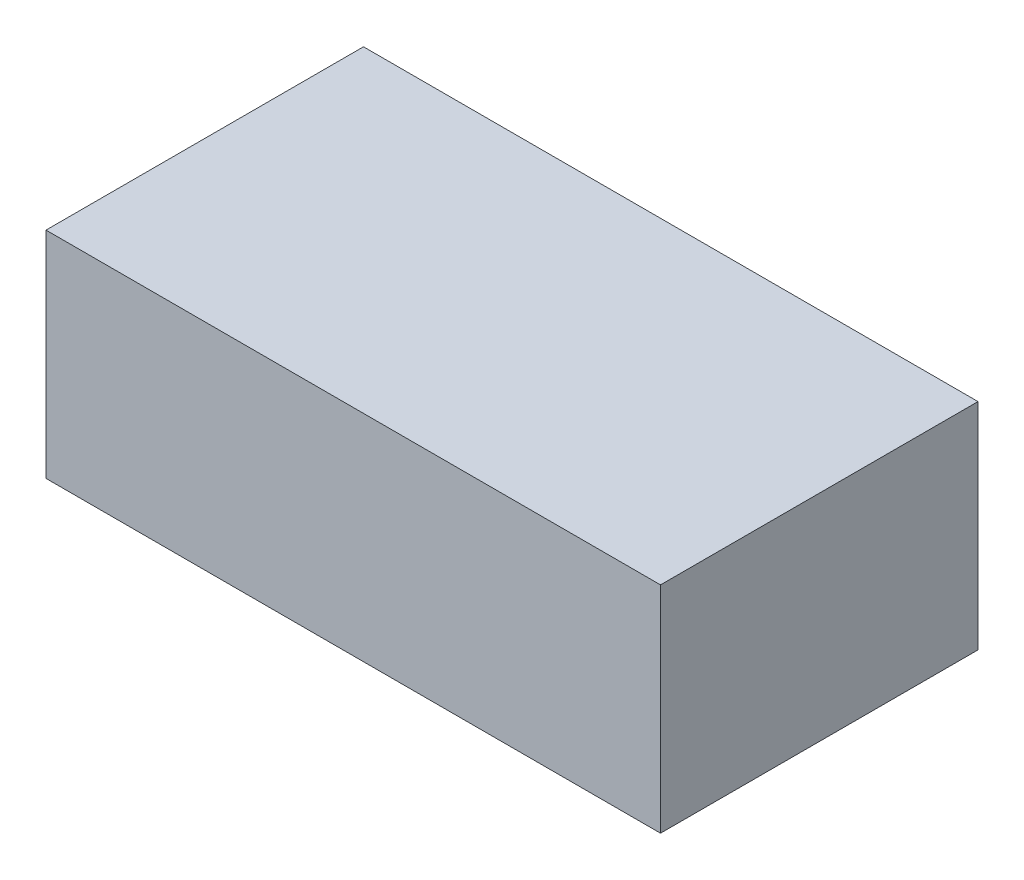
SolidWorks part; units mm, degrees
ref_plane "Front Plane" through (0, 0, 0) normal (0, 0, 1) x (1, 0, 0)
ref_plane "Top Plane" through (0, 0, 0) normal (0, 1, 0) x (1, 0, 0)
ref_plane "Right Plane" through (0, 0, 0) normal (1, 0, 0) x (0, 0, -1)
sketch "Sketch1" plane through (0, 0, 0) normal (0, 1, 0) x (1, 0, 0)
  line L1 (0, 0) -> (60, 0)
  line L2 (0, 0) -> (0, 31)
  line L3 (0, 31) -> (60, 31)
  line L4 (60, 0) -> (60, 31)
  dimension "D1" = 60
  dimension "D2" = 31
extrude "Boss-Extrude1" add sketch "Sketch1" along normal blind 21
equation "\"D1@Sketch1\"=60mm"
equation "\"D2@Sketch1\"=31mm"
equation "\"D1@Boss-Extrude1\"=21mm"
